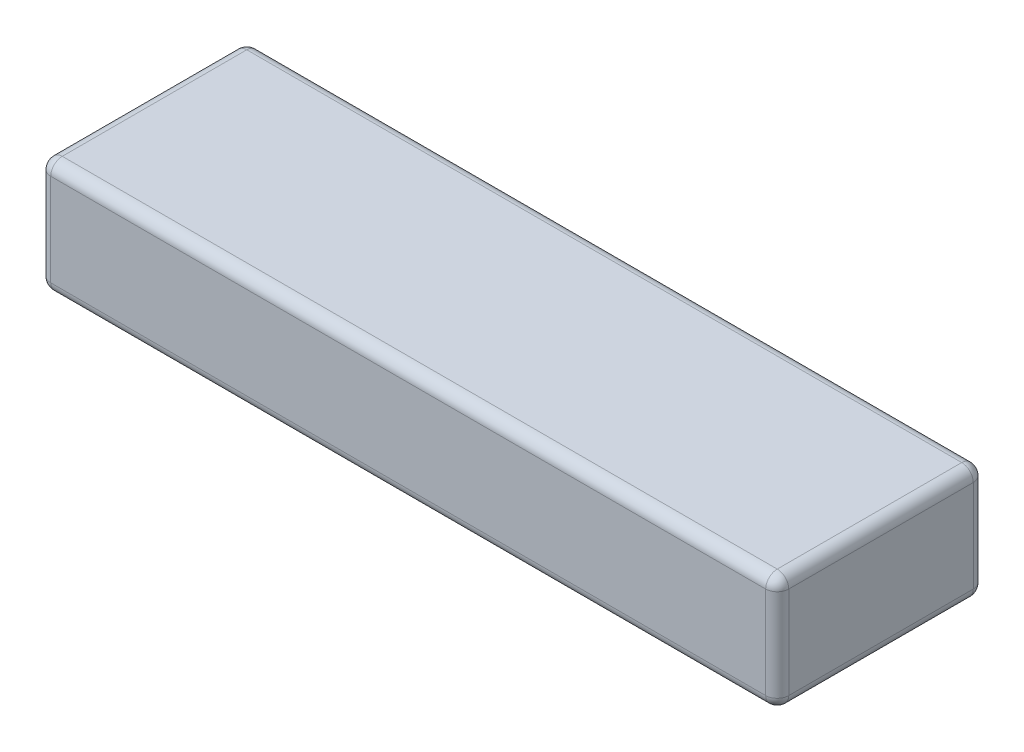
SolidWorks part; units mm, degrees
ref_plane "Front Plane" through (0, 0, 0) normal (0, 0, 1) x (1, 0, 0)
ref_plane "Top Plane" through (0, 0, 0) normal (0, 1, 0) x (1, 0, 0)
ref_plane "Right Plane" through (0, 0, 0) normal (1, 0, 0) x (0, 0, -1)
sketch "Sketch1" plane through (0, 0, 0) normal (0, 1, 0) x (1, 0, 0)
  line L1 (-80, -22.5) -> (80, -22.5)
  line L2 (-80, -22.5) -> (-80, 22.5)
  line L3 (-80, 22.5) -> (80, 22.5)
  line L4 (80, -22.5) -> (80, 22.5)
  line L5 (-80, -22.5) -> (80, 22.5) construction
  line L6 (-80, 22.5) -> (80, -22.5) construction
  point P0 (0, 0)
  dimension "D1" = 160
  dimension "D2" = 45
extrude "Boss-Extrude1" add sketch "Sketch1" along normal blind 25
fillet "Fillet1" radius 2.5 12 edges at (80, 12.5, -22.5) (-80, 12.5, -22.5) (-80, 12.5, 22.5) (80, 12.5, 22.5) (0, 25, 22.5) (-80, 25, 0) (0, 25, -22.5) (80, 25, 0) (0, 0, -22.5) (-80, 0, 0) (0, 0, 22.5) (80, 0, 0)
